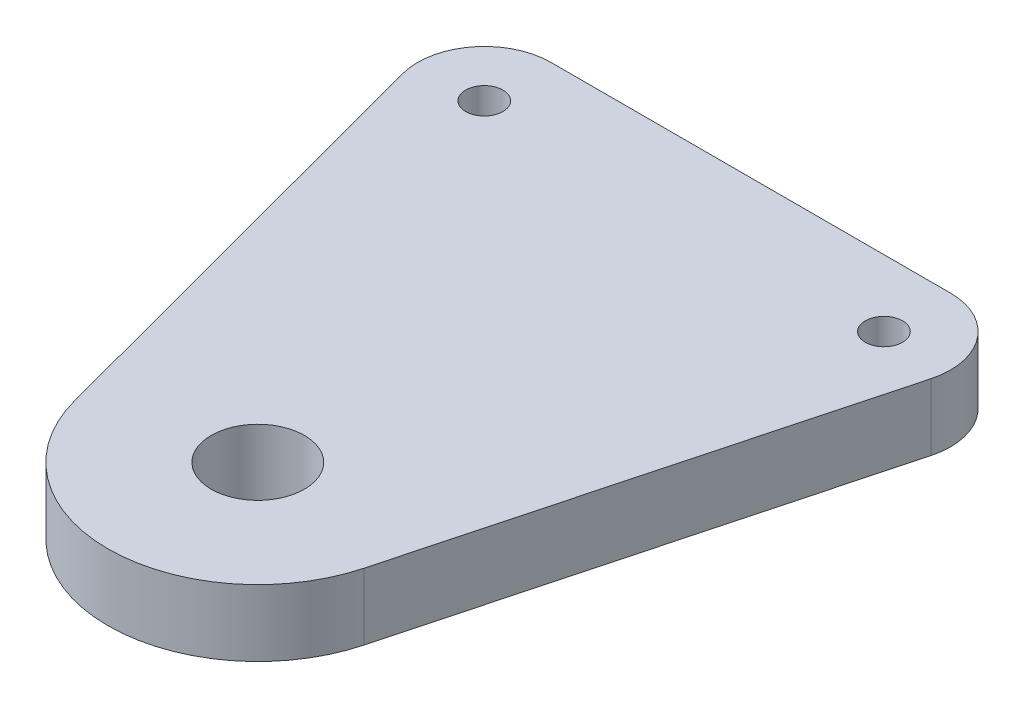
SolidWorks part; units mm, degrees
ref_plane "Front Plane" through (0, 0, 0) normal (0, 0, 1) x (1, 0, 0)
ref_plane "Top Plane" through (0, 0, 0) normal (0, 1, 0) x (1, 0, 0)
ref_plane "Right Plane" through (0, 0, 0) normal (1, 0, 0) x (0, 0, -1)
sketch "Sketch1" plane through (0, 0, 0) normal (0, 1, 0) x (1, 0, 0)
  line L0 (-15, 32) -> (15, 32) construction
  line L1 (-15, 37) -> (15, 37)
  line L2 (-15, 27) -> (15, 27) construction
  line L3 (-10.8703, -2.8982) -> (-19.8312, 30.7119)
  line L4 (19.8312, 30.7119) -> (10.8703, -2.8982)
  circle A0 centre (0, 0) radius 3.5
  arc A1 (-10.8703, -2.8982) -> (10.8703, -2.8982) centre (0, 0) ccw
  arc A2 (-15, 37) -> (-19.8312, 30.7119) centre (-15, 32) ccw
  arc A3 (19.8312, 30.7119) -> (15, 37) centre (15, 32) ccw
  arc A4 (-19.8312, 30.7119) -> (-15, 27) centre (-15, 32) ccw construction
  arc A5 (15, 27) -> (19.8312, 30.7119) centre (15, 32) ccw construction
  arc A6 (10.8703, -2.8982) -> (-10.8703, -2.8982) centre (0, 0) ccw construction
  circle A7 centre (-15, 32) radius 1.4
  circle A8 centre (15, 32) radius 1.4
  point P6 (0, 32)
  dimension "D1" = 7
  dimension "D2" = 22.5
  dimension "D4" = 5
  dimension "D6" = 2.8
  dimension "D3" = 30
  dimension "D5" = 37
extrude "Boss-Extrude1" add sketch "Sketch1" along normal blind 5
